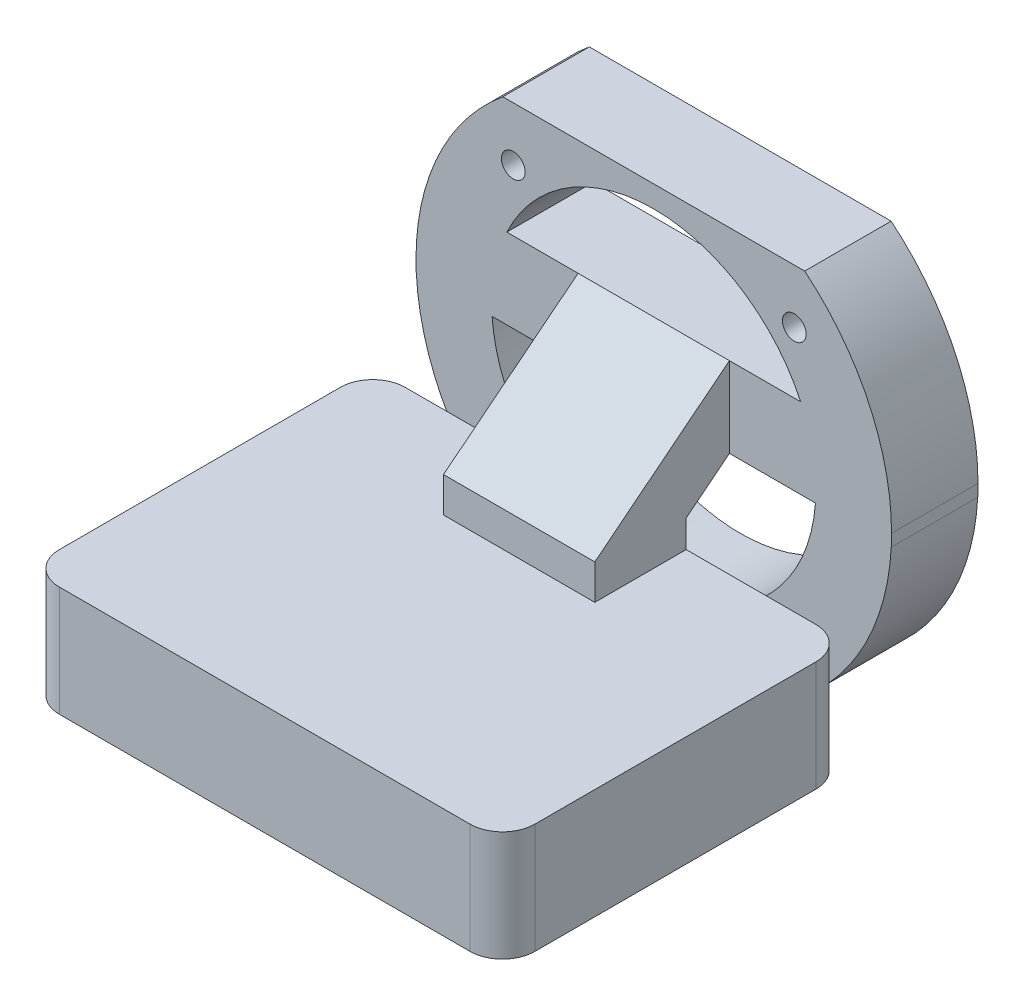
SolidWorks part; units mm, degrees
ref_plane "前视基准面" through (0, 0, 0) normal (0, 0, 1) x (1, 0, 0)
ref_plane "上视基准面" through (0, 0, 0) normal (0, 1, 0) x (1, 0, 0)
ref_plane "右视基准面" through (0, 0, 0) normal (1, 0, 0) x (0, 0, -1)
other "Configuration Table"
sketch "草图1" plane through (0, 0, 0) normal (0, 0, 1) x (1, 0, 0)
  line L1 (13.9642, -17) -> (-13.9642, -17)
  line L3 (13.9642, 17) -> (-13.9642, 17)
  line L7 (-13, -12) -> (13, -12) construction
  line L8 (-13, -12) -> (-13, 12) construction
  line L9 (-13, 12) -> (13, 12) construction
  line L10 (13, -12) -> (13, 12) construction
  line L11 (-13, -12) -> (13, 12) construction
  line L12 (-13, 12) -> (13, -12) construction
  arc A0 (-13.9642, 17) -> (-13.9642, -17) centre (0, 0) ccw
  circle A1 centre (0, 0) radius 15
  arc A2 (13.9642, -17) -> (13.9642, 17) centre (0, 0) ccw
  circle A3 centre (-13, 12) radius 1.1
  circle A4 centre (13, 12) radius 1.1
  circle A5 centre (13, -12) radius 1.1
  circle A6 centre (-13, -12) radius 1.1
  dimension "D1" = 44
  dimension "D2" = 30
  dimension "D6" = 2.2
  dimension "D3" = 34
  dimension "D4" = 26
  dimension "D5" = 24
extrude "凸台-拉伸1" add sketch "草图1" along normal blind 8
sketch "草图3" plane through (0, 0, 0) normal (1, 0, 0) x (0, 0, -1)
  line L0 (-12, -6.8) -> (-12, -4.2726)
  line L1 (-12, -17) -> (-44, -17)
  line L2 (-12, -17) -> (-12, -6.8)
  line L3 (-20.4555, -6.8) -> (-44, -6.8)
  line L4 (-44, -17) -> (-44, -6.8)
  line L5 (-12, -4.2726) -> (-8, -1.0934)
  line L6 (-8, 17) -> (-8, -17) construction
  line L8 (-8, 6.3401) -> (-20.4555, -3.5595)
  line L9 (-20.4555, -3.5595) -> (-20.4555, -6.8)
  line L11 (0, -17) -> (0, 17) construction
  line L12 (-8, -17) -> (0, -17) construction
  line L14 (-8, -1.0934) -> (0, -1.0934)
  line L16 (-8, 6.3401) -> (0, 6.3401)
  line L17 (0, -1.0934) -> (0, 6.3401)
  point P19 (-28, -17)
  dimension "D1" = 10.2
  dimension "D2" = 44
  dimension "D3" = 28
extrude "凸台-拉伸2" add sketch "草图3" along normal through all and the other way through all
sketch "草图5" plane through (-22, 0, 0) normal (-1, 0, 0) x (0, 0, 1)
  line L1 (20.4555, -6.8) -> (8, -6.8)
  line L2 (20.4555, -6.8) -> (20.4555, 6.3401)
  line L3 (20.4555, 6.3401) -> (8, 6.3401)
  line L4 (8, -6.8) -> (8, 6.3401)
extrude "切除-拉伸1" cut sketch "草图5" against normal blind 15
mirror "镜向1" about plane through (0, 0, 0) normal (1, 0, 0) of "切除-拉伸1"
sketch "草图6" plane through (0, 0, 8) normal (0, 0, 1) x (1, 0, 0)
  line L0 (21.0666, 6.3401) -> (22, 6.3401)
  line L1 (22, 6.3401) -> (22, 0)
  line L2 (-21.0666, 6.3401) -> (-22, 6.3401)
  line L3 (-22, 6.3401) -> (-22, 0)
  arc A0 (22, 0) -> (21.0666, 6.3401) centre (0, 0) ccw
  arc A1 (-21.0666, 6.3401) -> (-22, 0) centre (0, 0) ccw
extrude "切除-拉伸2" cut sketch "草图6" against normal blind 15
sketch "草图7" plane through (0, -17, 0) normal (0, -1, 0) x (1, 0, 0)
  circle A0 centre (0, 28) radius 4
  dimension "D1" = 8
extrude "凸台-拉伸3" add sketch "草图7" along normal blind 2
sketch "草图8" plane through (0, -19, 0) normal (0, -1, 0) x (1, 0, 0)
  circle A0 centre (0, 28) radius 3
  dimension "D1" = 6
extrude "切除-拉伸3" cut sketch "草图8" against normal blind 1
sketch "草图9" plane through (0, -18, 0) normal (0, -1, 0) x (1, 0, 0)
  circle A0 centre (0, 28) radius 1.5
  dimension "D1" = 3
dome "圆顶1" faces to dome 1 distance 1.5 reverse direction no elliptical dome no face at (0, -18, 25) parameters "D1"=1.5
fillet "圆角1" radius 3 4 edges at (-22, -11.9, 12) (-22, -11.9, 44) (22, -11.9, 12) (22, -11.9, 44)
